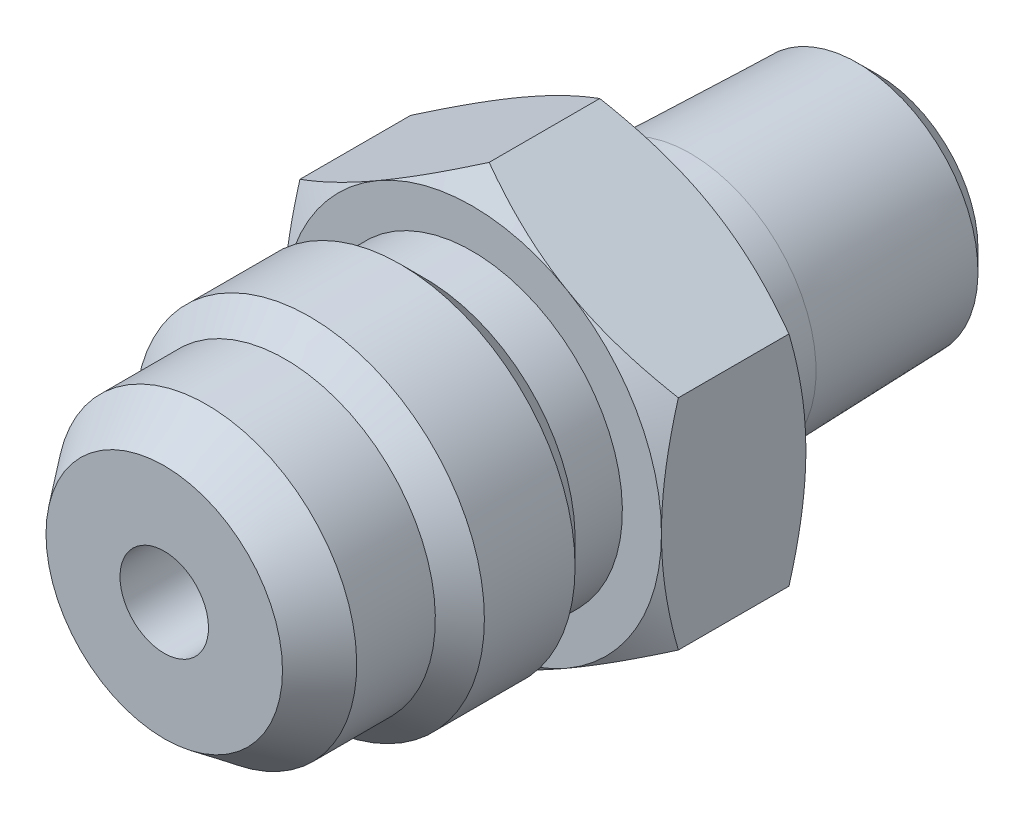
SolidWorks part; units mm, degrees
material "AISI 316 Stainless Steel Sheet (SS)"
ref_plane "Front" through (0, 0, 0) normal (0, 0, 1) x (1, 0, 0)
ref_plane "Top" through (0, 0, 0) normal (0, 1, 0) x (1, 0, 0)
ref_plane "Right" through (0, 0, 0) normal (1, 0, 0) x (0, 0, -1)
sketch "Sketch1" plane through (0, 0, 0) normal (1, 0, 0) x (0, 0, -1)
  line L0 (-19.4469, 0) -> (19.4469, 0) construction
  line L1 (-19.4469, 2.413) -> (-19.4469, 6.4481)
  line L2 (-19.4469, 6.4481) -> (-17.1383, 8.1877)
  line L3 (-17.1383, 8.1877) -> (-12.8508, 8.1877)
  line L4 (-12.8508, 8.1877) -> (-11.5135, 9.525)
  line L5 (-11.5135, 9.525) -> (-6.5681, 9.525)
  line L6 (-6.5681, 9.525) -> (-5.2308, 8.1877)
  line L7 (-5.2308, 8.1877) -> (-2.6511, 8.1877)
  line L8 (-19.4469, 6.4481) -> (-18.7873, 6.4481) construction
  line L9 (-18.7873, 6.4481) -> (-18.1277, 6.4481) construction
  line L10 (-2.6511, 8.1877) -> (-2.6511, 10.3187)
  line L11 (-2.6511, 10.3187) -> (5.2229, 10.3187)
  line L12 (5.2229, 10.3187) -> (5.2229, 6.858)
  line L13 (5.2229, 6.858) -> (9.2412, 6.858)
  line L14 (9.2412, 6.858) -> (18.3545, 6.5743)
  line L15 (19.4469, 5.4819) -> (19.4469, 2.413)
  line L16 (19.4469, 2.413) -> (-19.4469, 2.413)
  line L17 (-17.1383, 8.1877) -> (-19.4469, 8.1877) construction
  line L18 (-19.4469, 8.1877) -> (-19.4469, 6.4481) construction
  line L19 (-11.5135, 9.525) -> (-12.8508, 9.525) construction
  line L20 (-12.8508, 9.525) -> (-12.8508, 8.1877) construction
  line L21 (-6.5681, 9.525) -> (-5.2308, 9.525) construction
  line L22 (-5.2308, 9.525) -> (-5.2308, 8.1877) construction
  line L23 (9.2412, 6.858) -> (19.4469, 6.858) construction
  line L24 (18.3545, 6.5743) -> (19.4469, 5.4819)
  line L25 (18.3545, 6.5743) -> (19.4469, 6.5402) construction
  line L26 (19.4469, 5.4819) -> (19.4469, 6.5402) construction
  line L27 (19.4469, 6.5402) -> (19.4469, 6.858) construction
  line L28 (19.4469, 6.5402) -> (19.976, 5.6237) construction
  line L29 (19.976, 5.6237) -> (20.1524, 5.6237) construction
  line L30 (20.1524, 5.6237) -> (20.7549, 6.6672) construction
  line L31 (20.7549, 6.6672) -> (19.3736, 6.6672) construction
  line L32 (19.3736, 6.6672) -> (19.4469, 6.5402) construction
  line L33 (19.7115, 6.082) -> (20.417, 6.082) construction
  line L34 (20.0642, 6.082) -> (20.0642, 5.6237) construction
  line L35 (20.0642, 5.8528) -> (21.4753, 5.8528) construction
  line L36 (-12.8508, 9.525) -> (-19.4469, 9.525) construction
  line L37 (-19.4469, 9.525) -> (-19.4469, 8.1877) construction
  line L38 (-19.4469, 9.525) -> (-20.0422, 8.4939) construction
  line L39 (-20.0422, 8.4939) -> (-20.2406, 8.4939) construction
  line L40 (-20.2406, 8.4939) -> (-20.9093, 9.652) construction
  line L41 (-20.9093, 9.652) -> (-19.3736, 9.652) construction
  line L42 (-19.3736, 9.652) -> (-19.4469, 9.525) construction
  line L43 (-19.7445, 9.0094) -> (-20.5383, 9.0094) construction
  line L44 (-20.1414, 9.0094) -> (-20.1414, 8.4939) construction
  line L45 (-20.1414, 8.7517) -> (-21.7289, 8.7517) construction
  line L46 (-18.1277, 6.4481) -> (-17.4681, 6.4481) construction
  line L47 (-17.4681, 6.4481) -> (-16.8085, 6.4481) construction
  line L48 (-16.8085, 6.4481) -> (-16.1488, 6.4481) construction
  line L49 (-16.1488, 6.4481) -> (-15.4892, 6.4481) construction
  line L50 (-15.4892, 6.4481) -> (-14.8296, 6.4481) construction
  line L51 (-14.8296, 6.4481) -> (-14.17, 6.4481) construction
  line L52 (-14.17, 6.4481) -> (-13.5104, 6.4481) construction
  line L53 (-13.5104, 6.4481) -> (-12.8508, 6.4481) construction
  line L54 (-12.8508, 8.1877) -> (-12.8508, 6.4481) construction
  line L55 (-17.1383, 8.1877) -> (-17.1383, 6.4481) construction
  dimension "D1" = 37
  dimension "D3" = 45
  dimension "D4" = 1.783
  dimension "D2" = 0.127
  dimension "D5" = 60
  dimension "D6" = 0.1764
  dimension "D7" = 0.7056
  dimension "D8" = 1.0583
  dimension "D9" = 0.127
  dimension "D10" = 60
  dimension "D11" = 0.1984
  dimension "D12" = 0.7937
  dimension "D13" = 2.5797
revolve "Revolve1" add sketch "Sketch1" angle 360 about L0
sketch "Sketch2" plane through (0, 0, 2.6511) normal (0, 0, 1) x (1, 0, 0)
  line L1 (0, 11.9151) -> (-10.3188, 5.9575)
  line L2 (-10.3188, 5.9575) -> (-10.3188, -5.9575)
  line L3 (-10.3188, -5.9575) -> (0, -11.9151)
  line L4 (0, -11.9151) -> (10.3188, -5.9575)
  line L5 (10.3188, -5.9575) -> (10.3188, 5.9575)
  line L6 (10.3188, 5.9575) -> (0, 11.9151)
  circle A0 centre (0, 0) radius 10.3187 construction
  circle A1 centre (0, 0) radius 10.3187 construction
  circle A2 centre (0, 0) radius 10.1917
  dimension "D1" = 0.127
extrude "Boss-Extrude1" add sketch "Sketch2" against normal up to surface (7.874 mm away) up to face at (0, -10.3187, -5.2229)
sketch "Sketch3" plane through (0, 0, 0) normal (1, 0, 0) x (0, 0, -1)
  line L0 (-19.4469, 0) -> (19.4469, 0) construction
  line L1 (1.2859, 10.3187) -> (1.2859, 0) construction
  line L2 (-2.6511, 10.3187) -> (5.2229, 10.3187) construction
  line L3 (-2.6511, 10.3187) -> (-2.6511, 11.9151)
  line L4 (-2.6511, 11.9151) -> (-1.7295, 11.9151)
  line L5 (5.2229, 11.9151) -> (-2.6511, 11.9151) construction
  line L6 (-1.7295, 11.9151) -> (-2.6511, 10.3187)
  line L7 (4.3012, 11.9151) -> (5.2229, 10.3187)
  line L8 (5.2229, 11.9151) -> (4.3012, 11.9151)
  line L9 (5.2229, 10.3187) -> (5.2229, 11.9151)
  dimension "D1" = 30
revolve "Cut-Revolve1" cut sketch "Sketch3" angle 360 about L0
sketch "Sketch4" plane through (0, 0, 19.4469) normal (0, 0, 1) x (1, 0, 0)
  circle A0 centre (0, 0) radius 9.525 construction
  circle A1 centre (0, 0) radius 9.525
curve "Helix/Spiral1" pitch 1.5875 height 16.7957 turns 10.58
sketch "Sketch5" [suppressed] plane through (0, 0, 0) normal (1, 0, 0) x (0, 0, -1)
  line L0 (-19.3736, 9.652) -> (-20.0422, 8.4939)
  line L1 (-20.0422, 8.4939) -> (-20.2406, 8.4939)
  line L2 (-20.2406, 8.4939) -> (-20.9093, 9.652)
  line L3 (-20.9093, 9.652) -> (-19.3736, 9.652)
sweep "Sweep1" [suppressed] add profiles "Sketch5" path "Helix/Spiral1"
sketch "Sketch6" [suppressed] plane through (0, 0, -19.4469) normal (0, 0, -1) x (-1, 0, 0)
  circle A0 centre (0, 0) radius 6.5402
curve "Helix/Spiral2" [suppressed]
sketch "Sketch7" [suppressed] plane through (0, 0, 0) normal (1, 0, 0) x (0, 0, -1)
  line L0 (19.3736, 6.6672) -> (19.976, 5.6237)
  line L1 (19.976, 5.6237) -> (20.1524, 5.6237)
  line L2 (20.1524, 5.6237) -> (20.7549, 6.6672)
  line L3 (20.7549, 6.6672) -> (19.3736, 6.6672)
sweep "Sweep2" [suppressed] add profiles "Sketch7" path "Helix/Spiral2"
sketch "Sketch8" [suppressed] plane through (0, 0, 0) normal (1, 0, 0) x (0, 0, -1)
  line L0 (-19.4469, 0) -> (19.4469, 0) construction
  line L1 (-5.2308, -11.9151) -> (9.2412, -11.9151)
  line L2 (-5.2308, -11.9151) -> (-5.2308, 11.9151)
  line L3 (-5.2308, 11.9151) -> (9.2412, 11.9151)
  line L4 (9.2412, -11.9151) -> (9.2412, 11.9151)
  line L5 (-5.2308, -11.9151) -> (9.2412, 11.9151) construction
  line L6 (-5.2308, 11.9151) -> (9.2412, -11.9151) construction
  line L7 (4.3012, 11.9151) -> (-1.7295, 11.9151) construction
  point P0 (2.0052, 0)
extrude "Cut-Extrude1" [suppressed] cut sketch "Sketch8" against normal through all both and the other way through all
combine bodies "Combine1" [suppressed] operation type subtract main body 111 bodies to subtract 114 115
equation "\"D6@Sketch1\"=\"ThreadPitch2@Sketch1\"*.125"
equation "\"D7@Sketch1\"=\"ThreadPitch2@Sketch1\"*.5"
equation "\"D8@Sketch1\"=\"ThreadPitch2@Sketch1\"*.75"
equation "\"D11@Sketch1\"=\"ThreadPitch1@Sketch1\"*.125"
equation "\"D12@Sketch1\"=\"ThreadPitch1@Sketch1\"*.5"
equation "\"D4@Helix/Spiral1\"=\"ThreadPitch1@Sketch1\""
equation "\"D3@Helix/Spiral1\"=\"Length@Sketch1\"-(\"HexWidth@Sketch1\"+\"SideLength2@Sketch1\")"
equation "\"D4@Helix/Spiral2\"=\"ThreadPitch2@Sketch1\""
equation "\"D3@Helix/Spiral2\"=\"ThreadFTE2@Sketch1\"+\"ThreadPitch2@Sketch1\""
equation "\"D13@Sketch1\"=\"ThreadPitch1@Sketch1\"*1.625"
